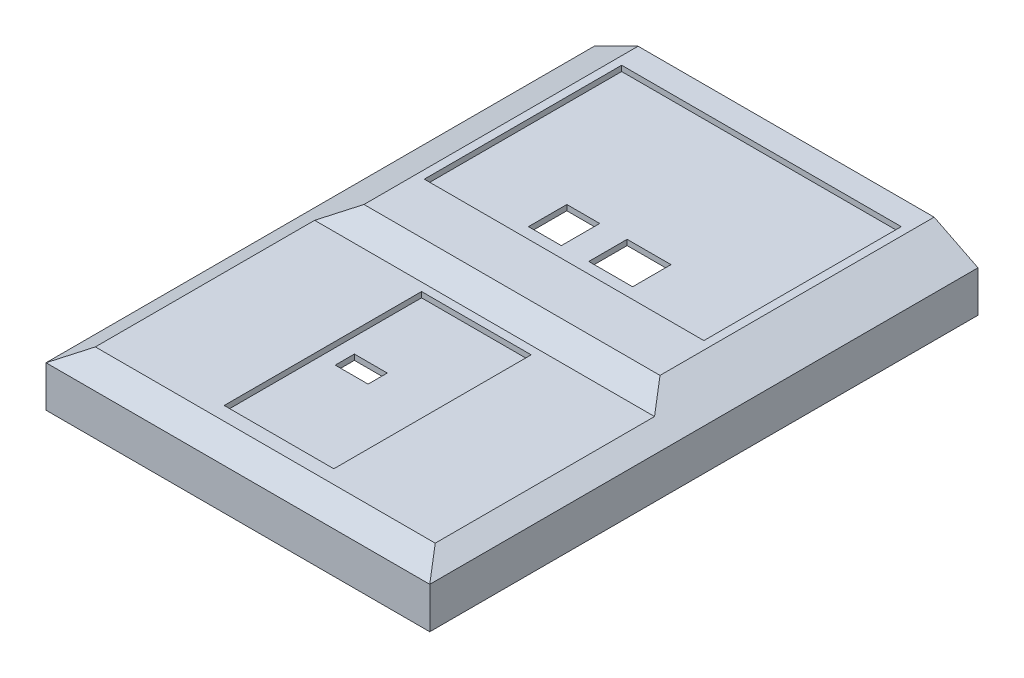
SolidWorks part; units mm, degrees
ref_plane "Ebene vorne" through (0, 0, 0) normal (0, 0, 1) x (1, 0, 0)
ref_plane "Ebene oben" through (0, 0, 0) normal (0, 1, 0) x (1, 0, 0)
ref_plane "Ebene rechts" through (0, 0, 0) normal (1, 0, 0) x (0, 0, -1)
sketch "Skizze1" plane through (0, 0, 0) normal (0, 0, 1) x (1, 0, 0)
  line L1 (-35, -7.5) -> (35, -7.5)
  line L2 (-35, -7.5) -> (-35, 7.5)
  line L3 (-35, 7.5) -> (35, 7.5)
  line L4 (35, -7.5) -> (35, 7.5)
  line L5 (-35, -7.5) -> (35, 7.5) construction
  line L6 (-35, 7.5) -> (35, -7.5) construction
  point P0 (0, 0)
  dimension "D1" = 70
  dimension "D2" = 15
extrude "Aufsatz-Linear austragen1" add sketch "Skizze1" along normal blind 100
sketch "Skizze2" plane through (0, 0, 100) normal (0, 0, 1) x (1, 0, 0)
  line L0 (-35, 7.5) -> (-35, 0)
  line L1 (-35, 7.5) -> (-35, -7.5) construction
  line L2 (-35, 0) -> (-20, 7.5)
  line L3 (35, 7.5) -> (-35, 7.5) construction
  line L4 (-20, 7.5) -> (-35, 7.5)
  dimension "D1" = 15
extrude "Schnitt-Linear austragen1" cut sketch "Skizze2" against normal up to surface (100 mm away) up to face at (0, 0, 0)
ref_plane "Ebene1" through (0, 0, 0) normal (-1, 0, 0) x (0, 0, 1)
mirror "Spiegeln1" about plane through (0, 0, 0) normal (-1, 0, 0) of "Schnitt-Linear austragen1"
sketch "Skizze4" plane through (-35, 0, 0) normal (-1, 0, 0) x (0, 0, 1)
  line L0 (100, 0) -> (95, 2)
  line L1 (95, 2) -> (55, 2)
  line L2 (55, 2) -> (50, 4)
  line L3 (50, 4) -> (0, 4)
  line L5 (0, 7.5) -> (100, 7.5) construction
  line L6 (0, 7.5) -> (100, 7.5)
  line L7 (100, 7.5) -> (100, 0)
  line L8 (0, 0) -> (0, 7.5) construction
  line L9 (0, 4) -> (0, 7.5)
  dimension "D1" = 2
  dimension "D2" = 2
  dimension "D3" = 40
  dimension "D4" = 50
extrude "Schnitt-Linear austragen3" cut sketch "Skizze4" against normal up to surface (70 mm away) up to face at (35, -3.75, 50)
shell "Wandung1" thickness 2 removed face at (0, -7.5, 50)
sketch "Skizze5" plane through (0, 2, 0) normal (0, 1, 0) x (1, 0, 0)
  line L0 (0, 4.125) -> (0, -4.125) construction
  line L1 (-10, -92.5) -> (10, -92.5)
  line L2 (-10, -92.5) -> (-10, -56.5)
  line L3 (-10, -56.5) -> (10, -56.5)
  line L4 (10, -92.5) -> (10, -56.5)
  line L5 (-10, -92.5) -> (10, -56.5) construction
  line L6 (-10, -56.5) -> (10, -92.5) construction
  line L7 (31, -55) -> (-31, -55) construction
  point P0 (0, -74.5)
  dimension "D1" = 36
  dimension "D2" = 20
  dimension "D3" = 1.5
extrude "Schnitt-Linear austragen4" cut sketch "Skizze5" against normal blind 1
sketch "Skizze6" plane through (0, 1, 0) normal (0, 1, 0) x (1, 0, 0)
  line L0 (-10, -56.5) -> (-10, -92.5) construction
  line L1 (-7.25, -71.5) -> (-1.25, -71.5)
  line L2 (-7.25, -71.5) -> (-7.25, -75)
  line L3 (-7.25, -75) -> (-1.25, -75)
  line L4 (-1.25, -71.5) -> (-1.25, -75)
  line L5 (10, -56.5) -> (-10, -56.5) construction
  dimension "D1" = 2.75
  dimension "D2" = 15
  dimension "D3" = 3.5
  dimension "D4" = 6
extrude "Schnitt-Linear austragen5" cut sketch "Skizze6" against normal up to surface (1 mm away) up to face at (0, 0, 74.6148)
sketch "Skizze7" plane through (0, 4, 0) normal (0, 1, 0) x (1, 0, 0)
  line L1 (25.5, -4.5) -> (-25.5, -4.5)
  line L2 (25.5, -4.5) -> (25.5, -40.5)
  line L3 (25.5, -40.5) -> (-25.5, -40.5)
  line L4 (-25.5, -4.5) -> (-25.5, -40.5)
  line L5 (25.5, -4.5) -> (-25.5, -40.5) construction
  line L6 (25.5, -40.5) -> (-25.5, -4.5) construction
  line L7 (27, -50) -> (27, 0) construction
  line L8 (27, 0) -> (-27, 0) construction
  point P0 (0, -22.5)
  dimension "D1" = 51
  dimension "D2" = 36
  dimension "D3" = 1.5
  dimension "D4" = 4.5
extrude "Schnitt-Linear austragen6" cut sketch "Skizze7" against normal blind 1
sketch "Skizze12" plane through (0, 3, 0) normal (0, 1, 0) x (1, 0, 0)
  line L0 (25.5, -40.5) -> (25.5, -4.5) construction
  line L1 (9.5, -37.5) -> (1.5, -37.5)
  line L2 (9.5, -37.5) -> (9.5, -30.5)
  line L3 (9.5, -30.5) -> (1.5, -30.5)
  line L4 (1.5, -37.5) -> (1.5, -30.5)
  line L5 (25.5, -4.5) -> (-25.5, -4.5) construction
  dimension "D1" = 7
  dimension "D2" = 8
  dimension "D3" = 16
  dimension "D4" = 26
extrude "Schnitt-Linear austragen8" cut sketch "Skizze12" against normal up to surface (1 mm away) up to face at (0, 2, 25.8074)
sketch "Skizze13" plane through (0, 0, 0) normal (0, 0, -1) x (-1, 0, 0)
  line L0 (2.5, -7.5) -> (-2.5, -7.5)
  line L1 (35, -7.5) -> (-35, -7.5) construction
  line L2 (-2.5, -7.5) -> (-2.5, -6.2)
  line L3 (-2.5, -6.2) -> (-7.5, -6.2)
  line L4 (-7.5, -6.2) -> (-7.5, -1.9)
  line L5 (-7.5, -1.9) -> (7.5, -1.9)
  line L6 (7.5, -1.9) -> (7.5, -6.2)
  line L7 (7.5, -6.2) -> (2.5, -6.2)
  line L8 (2.5, -6.2) -> (2.5, -7.5)
  line L9 (0, -4.125) -> (0, 4.125) construction
  dimension "D1" = 2.5
  dimension "D2" = 2.5
  dimension "D3" = 5
  dimension "D4" = 5
  dimension "D5" = 1.3
  dimension "D6" = 4.3
extrude "Schnitt-Linear austragen9" cut sketch "Skizze13" against normal blind 1
sketch "Skizze14" plane through (0, 3, 0) normal (0, 1, 0) x (1, 0, 0)
  line L0 (1.5, -30.5) -> (1.5, -37.5) construction
  line L1 (-3.5, -37.5) -> (-9.5, -37.5)
  line L2 (-3.5, -37.5) -> (-3.5, -30.5)
  line L3 (-3.5, -30.5) -> (-9.5, -30.5)
  line L4 (-9.5, -37.5) -> (-9.5, -30.5)
  line L5 (-25.5, -40.5) -> (25.5, -40.5) construction
  dimension "D1" = 5
  dimension "D2" = 6
  dimension "D3" = 3
  dimension "D4" = 7
extrude "Schnitt-Linear austragen10" cut sketch "Skizze14" against normal up to surface (1 mm away) up to face at (5.5, 2, 34)
